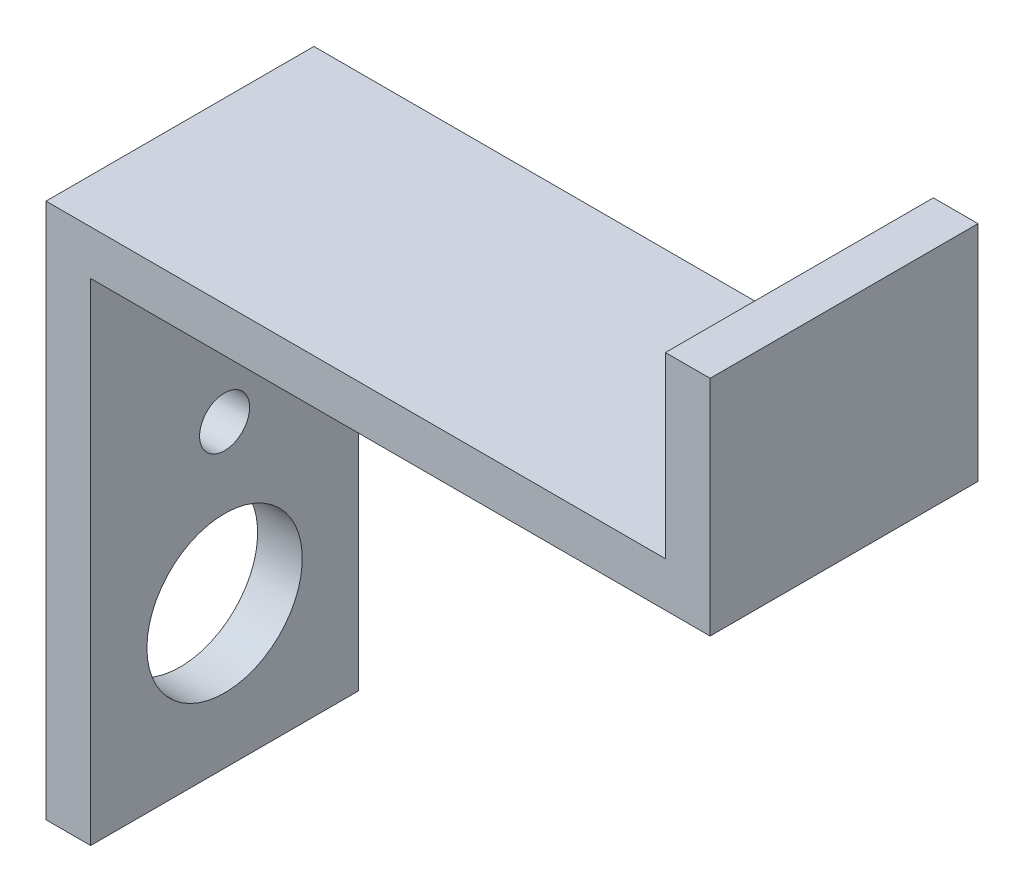
SolidWorks part; units mm, degrees
ref_plane "Front Plane" through (0, 0, 0) normal (0, 0, 1) x (1, 0, 0)
ref_plane "Top Plane" through (0, 0, 0) normal (0, 1, 0) x (1, 0, 0)
ref_plane "Right Plane" through (0, 0, 0) normal (1, 0, 0) x (0, 0, -1)
sketch "Sketch1" plane through (0, 0, 0) normal (0, 0, 1) x (1, 0, 0)
  line L0 (0, 0) -> (0, 76.2)
  line L5 (0, 76.2) -> (88.098, 76.2)
  line L6 (88.098, 76.2) -> (88.098, 101.6)
  line L7 (0, 0) -> (6.35, 0)
  line L8 (6.35, 0) -> (6.35, 76.2)
  line L9 (6.35, 76.2) -> (6.35, 69.85)
  line L10 (6.35, 69.85) -> (101.1141, 69.85)
  line L11 (88.098, 101.6) -> (94.448, 101.6)
  line L12 (94.448, 101.6) -> (94.448, 69.85)
  dimension "D1" = 25.4
  dimension "D2" = 76.2
extrude "Boss-Extrude1" add sketch "Sketch1" along normal blind 38.1 contours L7 L8 L5 L0 | L12 L11 L6 L5 L8 L10 region at (3.175, 38.1, 0) region at (47.224, 75.2636, 0)
sketch "Sketch2" plane through (0, 0, 0) normal (-1, 0, 0) x (0, 0, 1)
  line L0 (19.05, 20.32) -> (19.05, 42.672)
  line L1 (0, 0) -> (0, 76.2) construction
  line L2 (38.1, 0) -> (0, 0)
  line L3 (38.1, 0) -> (38.1, 50.8)
  line L4 (38.1, 50.8) -> (0, 50.8)
  line L5 (0, 0) -> (0, 50.8)
  line L6 (38.1, 0) -> (38.1, 20.32)
  line L7 (38.1, 20.32) -> (0, 20.32)
  circle A0 centre (19.05, 20.32) radius 11.049
  circle A1 centre (19.05, 42.672) radius 3.556
  point P13 (19.05, 20.32)
  dimension "D1" = 22.352
  dimension "D2" = 20.32
extrude "Cut-Extrude1" cut sketch "Sketch2" against normal blind 6.35 contours A0
extrude "Cut-Extrude2" cut sketch "Sketch2<4>" against normal blind 6.35 contours A1
sketch "Sketch2<4>" plane through (0, 0, 0) normal (-1, 0, 0) x (0, 0, 1) same geometry as "Sketch2"
